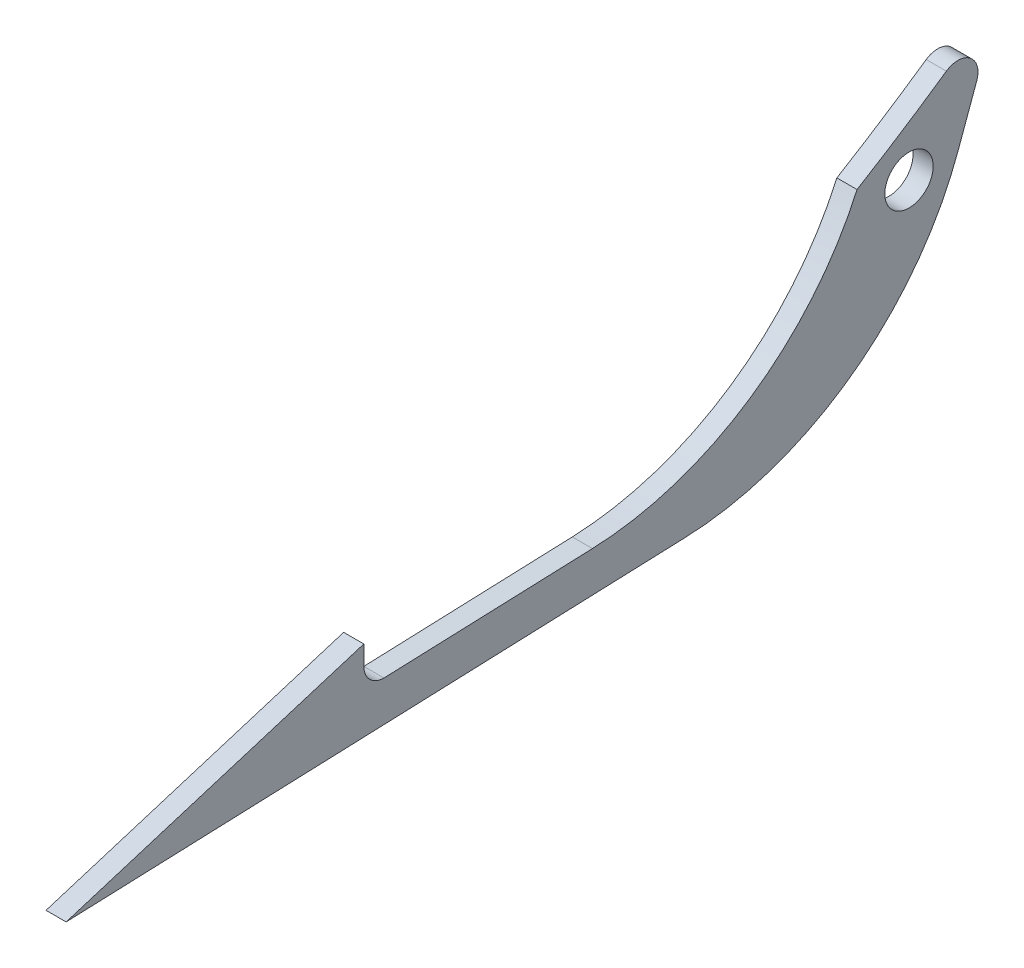
SolidWorks part; units mm, degrees
material "Ti-5Al-2.5Sn Отожженный (SS)"
ref_plane "Спереди" through (0, 0, 0) normal (0, 0, 1) x (1, 0, 0)
ref_plane "Сверху" through (0, 0, 0) normal (0, 1, 0) x (1, 0, 0)
ref_plane "Справа" through (0, 0, 0) normal (1, 0, 0) x (0, 0, -1)
sketch "Эскиз1" plane through (0, 0, 0) normal (1, 0, 0) x (0, 0, -1)
  line L0 (98.8217, -16.4384) -> (98.8217, -25.8841) construction
  line L1 (98.8217, -25.8841) -> (-151.1783, -25.8841) construction
  line L2 (126.2377, 58.8863) -> (98.8217, -16.4384)
  line L3 (-77.3456, -13.0873) -> (75.5394, -7.3109)
  line L4 (90.9757, 35.1) -> (75.5394, -7.3109)
  line L5 (-151.1783, -25.8841) -> (98.8217, -16.4384)
  line L6 (-151.1783, -25.8841) -> (-77.3456, -3.0802)
  line L7 (-77.3456, -3.0802) -> (-77.3456, -13.0873)
  circle A0 centre (103.8702, 30.6985) radius 6
  arc A1 (126.2377, 58.8863) -> (90.9757, 35.1) centre (-128.3125, 398.214) cw
  dimension "D1" = 250
  dimension "D2" = 15
extrude "Бобышка-Вытянуть1" add sketch "Эскиз1" along normal blind 5
fillet "Скругление1" radius 5 1 edges at (2.5, -13.0873, 77.3456)
fillet "Скругление2" radius 75 2 edges at (2.5, -16.4384, -98.8217) (2.5, -7.3109, -75.5394)
fillet "Скругление3" radius 5 1 edges at (2.5, 58.8863, -126.2377)
sketch "Эскиз4" plane through (5, 0, 0) normal (1, 0, 0) x (0, 0, -1)
  line L0 (-105.1876, -24.1464) -> (-31.3549, -1.3425)
  line L1 (-31.3549, -1.3425) -> (-31.3549, -6.1572)
  line L2 (-105.1876, -24.1464) -> (-31.3549, -21.3568)
  line L4 (-26.3549, -11.1572) -> (-31.3549, -21.3568)
  arc A0 (-26.3549, -11.1572) -> (-31.3549, -6.1572) centre (-26.3549, -6.1572) cw
extrude "Бобышка-Вытянуть2" add sketch "Эскиз4" against normal blind 5
sketch "Эскиз5" plane through (5, 0, 0) normal (1, 0, 0) x (0, 0, -1)
  line L0 (-38.4715, -3.5406) -> (-146.9832, -37.0554)
  line L1 (-31.3549, -1.3425) -> (-68.2712, -12.7445) construction
  line L2 (-175.3258, -14.8706) -> (-146.9832, -37.0554)
  line L3 (-38.4715, -3.5406) -> (-65.7323, 27.7483)
  line L4 (-65.7323, 27.7483) -> (-175.3258, -14.8706)
extrude "Вырез-Вытянуть2" cut sketch "Эскиз5" against normal through all
